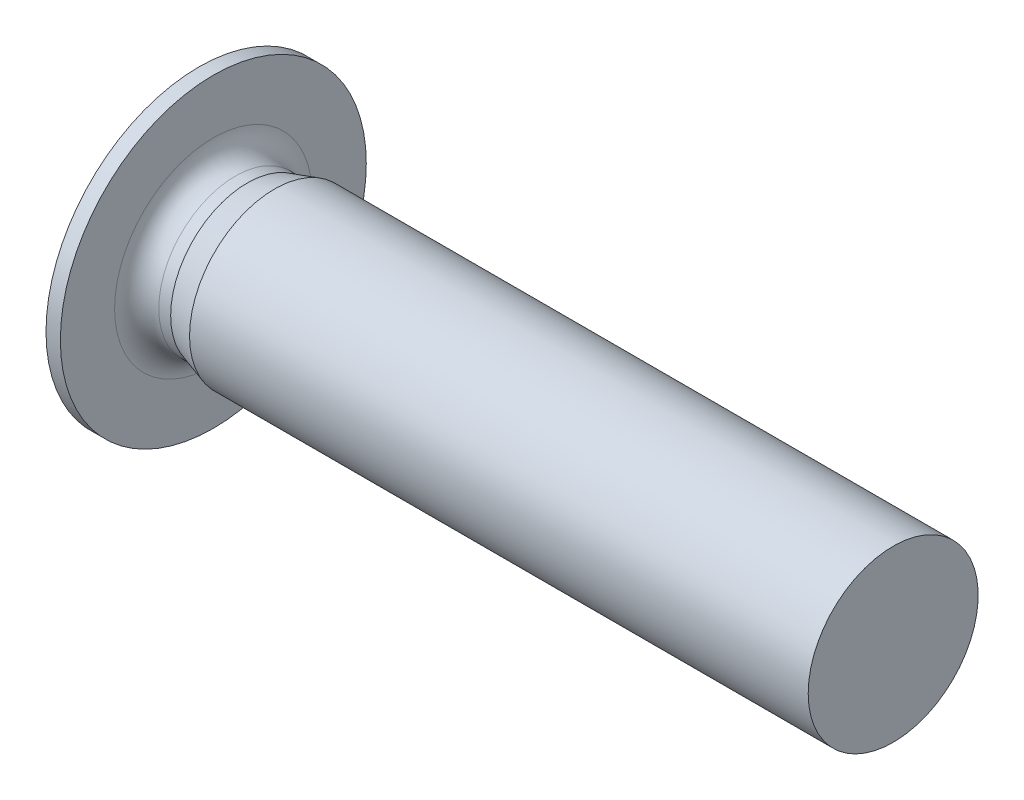
SolidWorks part; units mm, degrees
ref_plane "Front Plane" through (0, 0, 0) normal (0, 0, 1) x (1, 0, 0)
ref_plane "Top Plane" through (0, 0, 0) normal (0, 1, 0) x (1, 0, 0)
ref_plane "Right Plane" through (0, 0, 0) normal (1, 0, 0) x (0, 0, -1)
ref_axis "Axis_X" through (-88.99, 0, 0) along (1, 0, 0)
ref_axis "Axis_Y" through (0, 55, 0) along (0, -1, 0)
ref_axis "Axis_Z" through (0, 0, -88.99) along (0, 0, 1)
sketch "Sketch1" plane through (0, 0, 0) normal (0, 0, 1) x (1, 0, 0)
  line L0 (-1, 0) -> (20, 0)
  line L1 (20, 0) -> (20, 2.5)
  line L2 (20, 2.5) -> (1.8, 2.5)
  line L3 (1.8, 2.5) -> (1, 2.255)
  line L4 (1, 2.255) -> (0, 2.255)
  line L5 (0, 2.255) -> (0, 4.5)
  line L6 (0, 4.5) -> (-0.4226, 4.5)
  line L7 (-0.4226, 4.5) -> (-1, 3.5)
  line L8 (-1, 3.5) -> (-1, 0)
  line L9 (-1, 0) -> (20, 0) construction
  dimension "FIX_1" = 30
  dimension "MSM_1" = 7
  dimension "A" = 9
  dimension "MSM_2" = 4.51
  dimension "M" = 5
  dimension "MSM_3" = 0.8
  dimension "L" = 20
  dimension "E" = 1
  dimension "E_s" = 1.8
revolve "Revolve1" add sketch "Sketch1" angle 360 about L9
sketch "Sketch2" plane through (-1, 0, 0) normal (-1, 0, 0) x (0, 0, 1)
  line L1 (-1.4434, 0) -> (-0.7217, -1.25)
  line L2 (-0.7217, -1.25) -> (0.7217, -1.25)
  line L3 (0.7217, -1.25) -> (1.4434, 0)
  line L4 (1.4434, 0) -> (0.7217, 1.25)
  line L5 (0.7217, 1.25) -> (-0.7217, 1.25)
  line L6 (-0.7217, 1.25) -> (-1.4434, 0)
  circle A0 centre (0, 0) radius 1.25 construction
  dimension "B" = 2.5
extrude "Cut-Extrude1" cut sketch "Sketch2" against normal blind 1.6
sketch "Sketch3" plane through (0, 0, 0) normal (0, 0, 1) x (1, 0, 0)
  line L0 (0, 0) -> (-1, 0) construction
  line L1 (0.6, -1.25) -> (0.6, 0)
  line L2 (0.6, 0) -> (0.6, -1.25) construction
  line L3 (0.6, 0) -> (1.3511, 0)
  line L4 (1.3511, 0) -> (0.6, -1.25)
  line L5 (-1, 0) -> (-1, -1.25) construction
  dimension "FIX_3" = 59
  dimension "B" = 2.5
revolve "Cut-Revolve1" cut sketch "Sketch3" angle 360 about L0
fillet "Fillet1" radius 0.65 1 edges at (0, 0, 2.255)
equation "\"Factor\"= 1.082532"
equation "\"ATL_1@Thread1\" = \"L@Sketch1\" - \"E_s@Sketch1\""
equation "\"M\"=5"
equation "\"Pitch\"= iif ( \"M\" = 2 , 0.4 , iif ( \"M\" = 2.5 , 0.45 , iif ( \"M\" = 3 , 0.5 , iif ( \"M\" = 4 , 0.7 , iif ( \"M\" = 5 , 0.8 , 1 ) ) ) ) )"
equation "\"ATD_1\"= round ( \"M\" - \"Factor\" * \"Pitch\" , 3 )"
